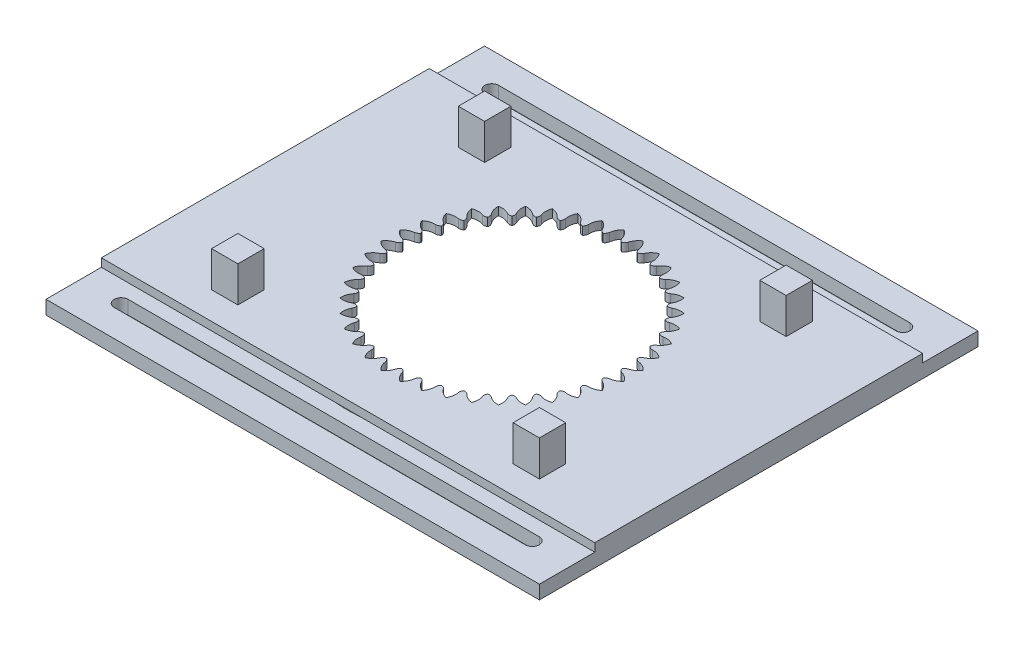
SolidWorks part; units mm, degrees
ref_plane "Front Plane" through (0, 0, 0) normal (0, 0, 1) x (1, 0, 0)
ref_plane "Top Plane" through (0, 0, 0) normal (0, 1, 0) x (1, 0, 0)
ref_plane "Right Plane" through (0, 0, 0) normal (1, 0, 0) x (0, 0, -1)
sketch "Sketch1" plane through (0, 0, 0) normal (0, 1, 0) x (1, 0, 0)
  line L1 (-114.3, -101.6) -> (114.3, -101.6)
  line L2 (-114.3, -101.6) -> (-114.3, 101.6)
  line L3 (-114.3, 101.6) -> (114.3, 101.6)
  line L4 (114.3, -101.6) -> (114.3, 101.6)
  line L5 (-114.3, -101.6) -> (114.3, 101.6) construction
  line L6 (-114.3, 101.6) -> (114.3, -101.6) construction
  point P0 (0, 0)
  dimension "D1" = 228.6
  dimension "D2" = 203.2
extrude "Boss-Extrude1" add sketch "Sketch1" along normal blind 10.16
sketch "Sketch3" plane through (0, 10.16, 0) normal (0, 1, 0) x (1, 0, 0)
  line L0 (-75.946, -63.246) -> (-75.946, -76.2) construction
  line L9 (-75.946, -63.246) -> (-63.754, -63.246)
  line L10 (-75.946, -63.246) -> (-75.946, -51.054)
  line L11 (-75.946, -51.054) -> (-63.754, -51.054)
  line L12 (-63.754, -63.246) -> (-63.754, -51.054)
  line L17 (-75.946, 51.054) -> (-63.754, 51.054)
  line L18 (0, 0) -> (-114.3, 0) construction
  line L19 (-114.3, 101.6) -> (-114.3, -101.6) construction
  line L20 (-75.946, 51.054) -> (-75.946, 63.246)
  line L21 (-75.946, 63.246) -> (-63.754, 63.246)
  line L22 (-63.754, 51.054) -> (-63.754, 63.246)
  line L23 (63.754, 51.054) -> (75.946, 51.054)
  line L24 (63.754, 51.054) -> (63.754, 63.246)
  line L25 (63.754, 63.246) -> (75.946, 63.246)
  line L26 (75.946, 51.054) -> (75.946, 63.246)
  line L27 (63.754, -51.054) -> (75.946, -51.054)
  line L28 (63.754, -51.054) -> (63.754, -63.246)
  line L29 (63.754, -63.246) -> (75.946, -63.246)
  line L30 (75.946, -51.054) -> (75.946, -63.246)
  line L31 (88.9, 76.2) -> (-88.9, 76.2) construction
  line L32 (88.9, 76.2) -> (88.9, -76.2) construction
  line L33 (88.9, -76.2) -> (-88.9, -76.2) construction
  line L34 (-88.9, 76.2) -> (-88.9, -76.2) construction
  line L35 (88.9, 76.2) -> (-88.9, -76.2) construction
  line L36 (88.9, -76.2) -> (-88.9, 76.2) construction
  line L37 (-75.946, -63.246) -> (-88.9, -63.246) construction
  line L38 (75.946, 63.246) -> (75.946, 76.2) construction
  line L39 (75.946, 63.246) -> (88.9, 63.246) construction
  dimension "D1" = 177.8
  dimension "D2" = 12.192
  dimension "D3" = 152.4
  dimension "D4" = 12.954
extrude "Boss-Extrude2" add sketch "Sketch3" along normal blind 16.51
ref_axis "Axis1" through (0, 28.0035, 0) along (0, -1, 0)
sketch "Sketch4" plane through (0, 10.16, 0) normal (0, 1, 0) x (1, 0, 0)
  circle A0 centre (0, 0) radius 56.6737
  circle A1 centre (0, 0) radius 53.975
  circle A2 centre (0, 0) radius 50.6016
  dimension "D1" = 107.95
  dimension "D2" = 113.3475
  dimension "D3" = 6.0722
extrude "Cut-Extrude3" cut sketch "Sketch4" against normal through all contours A0
sketch "Sketch6" plane through (0, 10.16, 0) normal (0, 1, 0) x (1, 0, 0)
  line L0 (0, 0) -> (0, 56.6738) construction
  line L1 (-2.119, 53.9334) -> (2.119, 53.9334) construction
  line L2 (-1.1806, 50.5878) -> (0, 0) construction
  line L3 (-3.9932, 57.1796) -> (0, 50.2631) construction
  line L4 (0, 0) -> (4.4466, 56.499) construction
  line L5 (2.119, 53.9334) -> (6.3441, 53.6009) construction
  arc A0 (-1.1806, 50.5878) -> (-6.7063, 57.2825) centre (-8.1974, 50.424) ccw
  circle A1 centre (0, 0) radius 56.6738 construction
  arc A2 (1.1806, 50.5878) -> (6.7063, 57.2825) centre (8.1974, 50.424) cw
  arc A4 (1.1806, 50.5878) -> (-1.1806, 50.5878) centre (0, 0) ccw
  circle A6 centre (0, 0) radius 53.975 construction
  circle A11 centre (0, 0) radius 50.6016 construction
  arc A12 (6.7063, 57.2825) -> (-6.7063, 57.2825) centre (0, 0) ccw
  point P18 (4.2316, 53.7671)
  dimension "D2" = 30
  dimension "D3" = 4.5
extrude "Boss-Extrude3" add sketch "Sketch6" against normal up to surface (10.16 mm away) up to face at (0, 0, 56.6738)
fillet "Fillet1" radius 2.54 2 edges at (1.1806, 5.08, -50.5878) (-1.1806, 5.08, -50.5878)
pattern_circular "CirPattern3" count 40 over 360 about axis through (0, 0, 0) along (0, 1, 0) of "Boss-Extrude3", "Fillet1"
sketch "Sketch9" plane through (0, 10.16, 0) normal (0, 1, 0) x (1, 0, 0)
  line L0 (-95.25, 85.852) -> (95.25, 85.852) construction
  line L1 (-95.25, 89.0905) -> (95.25, 89.0905)
  line L2 (-95.25, 82.6135) -> (95.25, 82.6135)
  line L3 (-95.25, -85.852) -> (-114.3, -85.852) construction
  line L4 (-114.3, 101.6) -> (-114.3, -101.6) construction
  line L7 (-14.6685, 0) -> (14.6685, 0) construction
  line L8 (-95.25, -85.852) -> (95.25, -85.852) construction
  line L9 (-95.25, -89.0905) -> (95.25, -89.0905)
  line L10 (-95.25, -82.6135) -> (95.25, -82.6135)
  line L11 (95.25, -85.852) -> (114.3, -85.852) construction
  line L12 (114.3, -101.6) -> (114.3, 101.6) construction
  arc A0 (-95.25, 89.0905) -> (-95.25, 82.6135) centre (-95.25, 85.852) ccw
  arc A1 (95.25, 82.6135) -> (95.25, 89.0905) centre (95.25, 85.852) ccw
  arc A2 (-95.25, -89.0905) -> (-95.25, -82.6135) centre (-95.25, -85.852) cw
  arc A3 (95.25, -82.6135) -> (95.25, -89.0905) centre (95.25, -85.852) cw
  point P2 (0, 85.852)
  point P19 (0, -85.852)
  dimension "D1" = 6.477
  dimension "D2" = 171.704
  dimension "D3" = 19.05
extrude "Cut-Extrude4" cut sketch "Sketch9" against normal through all
sketch "Sketch10" plane through (0, 0, 0) normal (0, -1, 0) x (1, 0, 0)
  circle A0 centre (0, 0) radius 76.2
  dimension "D1" = 152.4
extrude "Cut-Extrude5" cut sketch "Sketch10" against normal blind 6.35
sketch "Sketch12" plane through (0, 10.16, 0) normal (0, 1, 0) x (1, 0, 0)
  line L0 (-114.3, 101.6) -> (-114.3, -101.6) construction
  line L1 (-114.3, -75.946) -> (114.3, -75.946)
  line L2 (-114.3, -75.946) -> (-114.3, -101.6)
  line L3 (-114.3, -101.6) -> (114.3, -101.6)
  line L4 (114.3, -75.946) -> (114.3, -101.6)
  line L5 (-63.754, 63.246) -> (-75.946, 63.246) construction
  line L6 (-114.3, 75.946) -> (114.3, 75.946)
  line L7 (-114.3, 75.946) -> (-114.3, 101.6)
  line L8 (-114.3, 101.6) -> (114.3, 101.6)
  line L9 (114.3, 75.946) -> (114.3, 101.6)
  dimension "D1" = 12.7
extrude "Cut-Extrude6" cut sketch "Sketch12" against normal blind 3.81
equation "\"Module\"= \"Root Diameter\" / \"Num of Teeth\""
equation "\"Num of Teeth\"= 40"
equation "\"Press Angle\"= 30"
equation "\"Root Diameter\"= 4.25"
equation "\"D1@Sketch4\"=\"Root Diameter\""
equation "\"D2@Sketch4\"=(\"Num of Teeth\" + 2)*\"Module\""
equation "\"D3@Sketch4\"=\"Module\"*(if(\"Module\"=>-1.25,2.25,2.4))"
equation "\"D3@Sketch6\"=180/\"Num of Teeth\""
equation "\"D2@Sketch6\"=\"Press Angle\""
equation "\"D1@CirPattern3\"=\"Num of Teeth\""
equation "\"Circular Pitch\"= 3.1415 * \"Root Diameter\" / \"Num of Teeth\""
